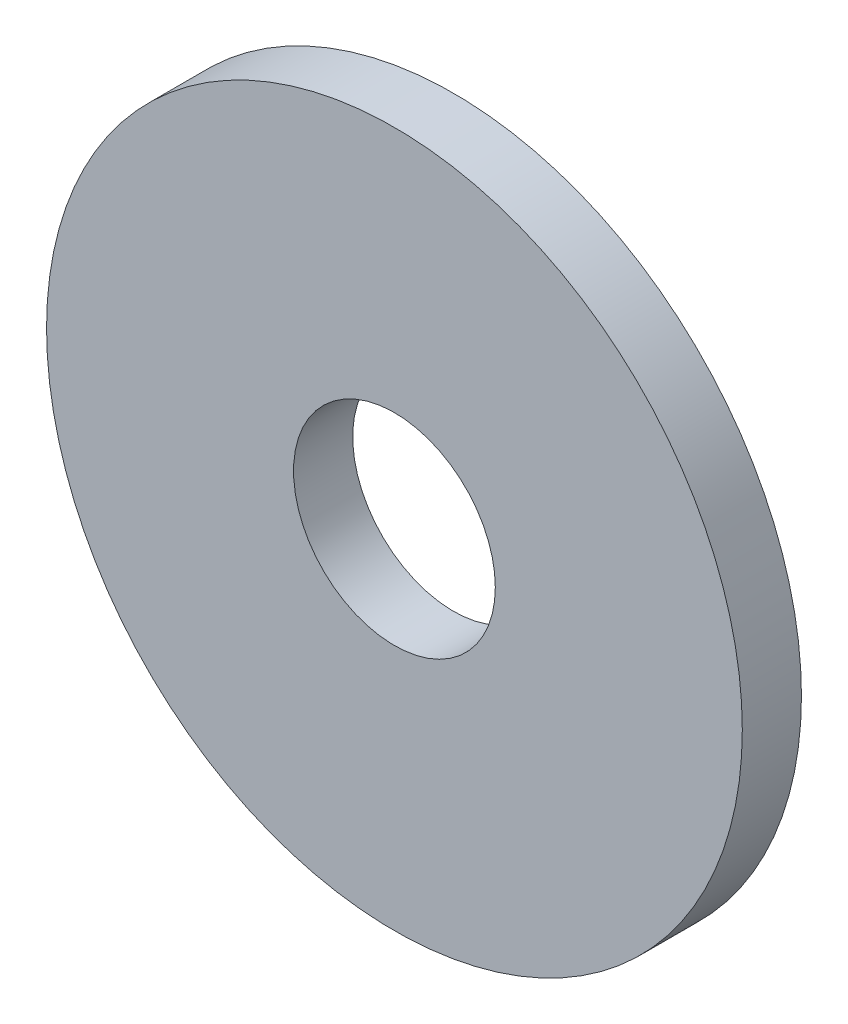
SolidWorks part; units mm, degrees
ref_plane "Front Plane" through (0, 0, 0) normal (0, 0, 1) x (1, 0, 0)
ref_plane "Top Plane" through (0, 0, 0) normal (0, 1, 0) x (1, 0, 0)
ref_plane "Right Plane" through (0, 0, 0) normal (1, 0, 0) x (0, 0, -1)
sketch "Sketch1" plane through (0, 0, 0) normal (0, 0, 1) x (1, 0, 0)
  circle A0 centre (0, 0) radius 10
  circle A1 centre (0, 0) radius 2.9
  dimension "D1" = 5.8
  dimension "D2" = 20
extrude "Boss-Extrude1" add sketch "Sketch1" along normal blind 1.7
equation "\"smallPulleyTeeth\"= 15"
equation "\"largePulleyTeeth\"= 30"
equation "\"eighthThick\"= 2.9mm"
equation "\"sixteenthThick\" = 1.7mm"
equation "\"wheelEighthThick\"=3.0mm"
equation "\"quarterThick\"=5.6mm"
equation "\"OD\" = 150mm"
equation "\"puckAngle\" = 60.5deg"
equation "\"puckDiam\" = 76.5mm"
equation "\"axlePress\" = 5.8mm"
equation "\"D1@Sketch1\"=\"axlePress\""
equation "\"D1@Boss-Extrude1\"=\"sixteenthThick\""
